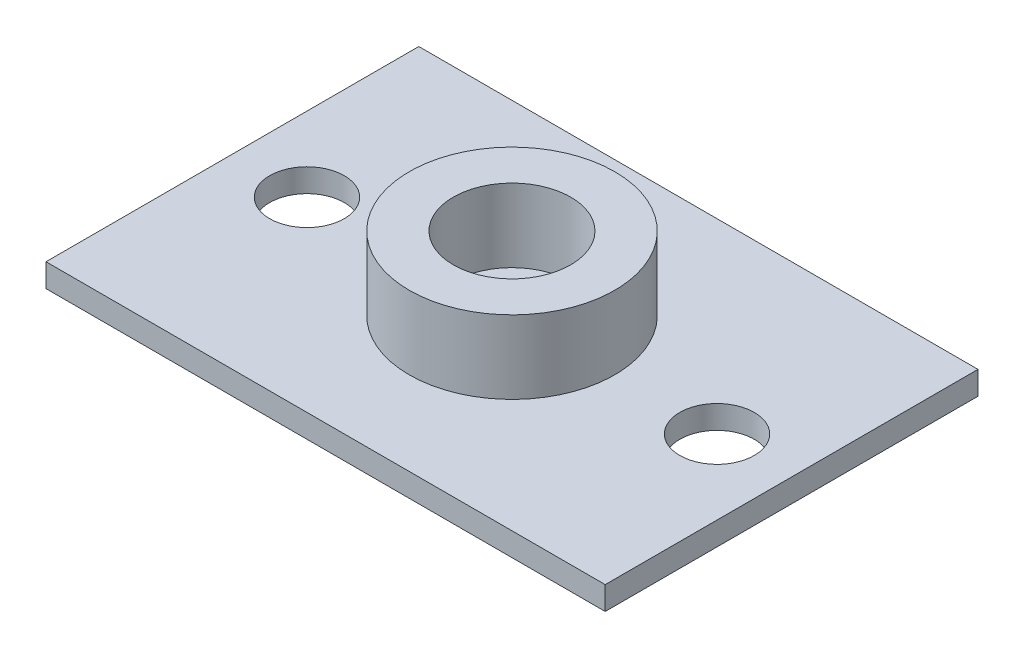
SolidWorks part; units mm, degrees
ref_plane "前视" through (0, 0, 0) normal (0, 0, 1) x (1, 0, 0)
ref_plane "上视" through (0, 0, 0) normal (0, 1, 0) x (1, 0, 0)
ref_plane "右视" through (0, 0, 0) normal (1, 0, 0) x (0, 0, -1)
sketch "Sketch1" plane through (0, 0, 0) normal (0, 1, 0) x (1, 0, 0)
  line L1 (-25.8417, 12.7) -> (12.2583, 12.7)
  line L2 (-25.8417, 12.7) -> (-25.8417, -12.7)
  line L3 (-25.8417, -12.7) -> (12.2583, -12.7)
  line L4 (12.2583, 12.7) -> (12.2583, -12.7)
  dimension "D1" = 25.4
  dimension "D2" = 38.1
extrude "Boss-Extrude1" add sketch "Sketch1" along normal blind 1.5875
ref_point "Point1"
sketch "Sketch3" plane through (0, 1.5875, 0) normal (0, 1, 0) x (1, 0, 0)
  circle A0 centre (-6.7917, 0) radius 7
  circle A1 centre (-6.7917, 0) radius 4
extrude "Boss-Extrude2" add sketch "Sketch3" along normal blind 4.99
ref_axis "Axis1" through (12.2583, 1.5875, 0) along (-1, 0, 0)
sketch "Sketch4" plane through (0, 1.5875, 0) normal (0, 1, 0) x (1, 0, 0)
  line L0 (12.2583, -12.7) -> (12.2583, 12.7) construction
  line L1 (-25.8417, 12.7) -> (-25.8417, -12.7) construction
  circle A0 centre (7.1783, 0) radius 2.54
  circle A1 centre (-20.7617, 0) radius 2.54
  point P0 (7.1783, 0)
  point P1 (12.2583, 0)
  point P4 (-20.7617, 0)
  dimension "D1" = 5.08
  dimension "D2" = 5.08
extrude "Cut-Extrude1" cut sketch "Sketch4" against normal through all
